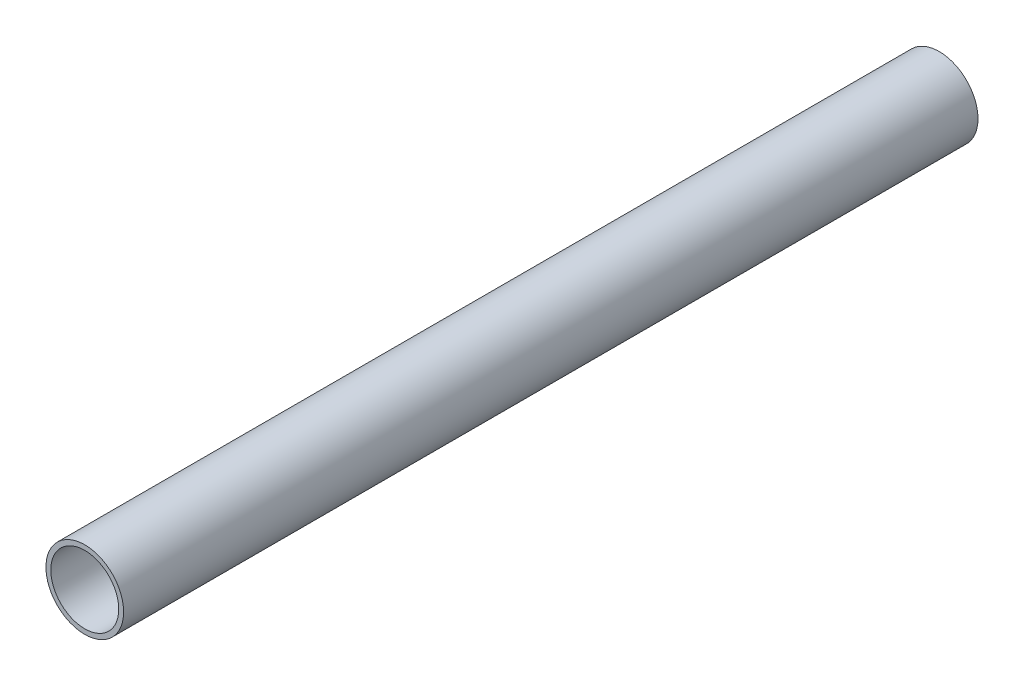
SolidWorks part; units mm, degrees
material "PC High Viscosity"
ref_plane "Front Plane" through (0, 0, 0) normal (0, 0, 1) x (1, 0, 0)
ref_plane "Top Plane" through (0, 0, 0) normal (0, 1, 0) x (1, 0, 0)
ref_plane "Right Plane" through (0, 0, 0) normal (1, 0, 0) x (0, 0, -1)
sketch "Sketch1" plane through (0, 0, 0) normal (0, 0, 1) x (1, 0, 0)
  circle A0 centre (0, 0) radius 22.225
  circle A1 centre (0, 0) radius 25.4
  dimension "D1" = 50.8
  dimension "D2" = 44.45
extrude "Boss-Extrude1" add sketch "Sketch1" along normal mid plane 558.8
